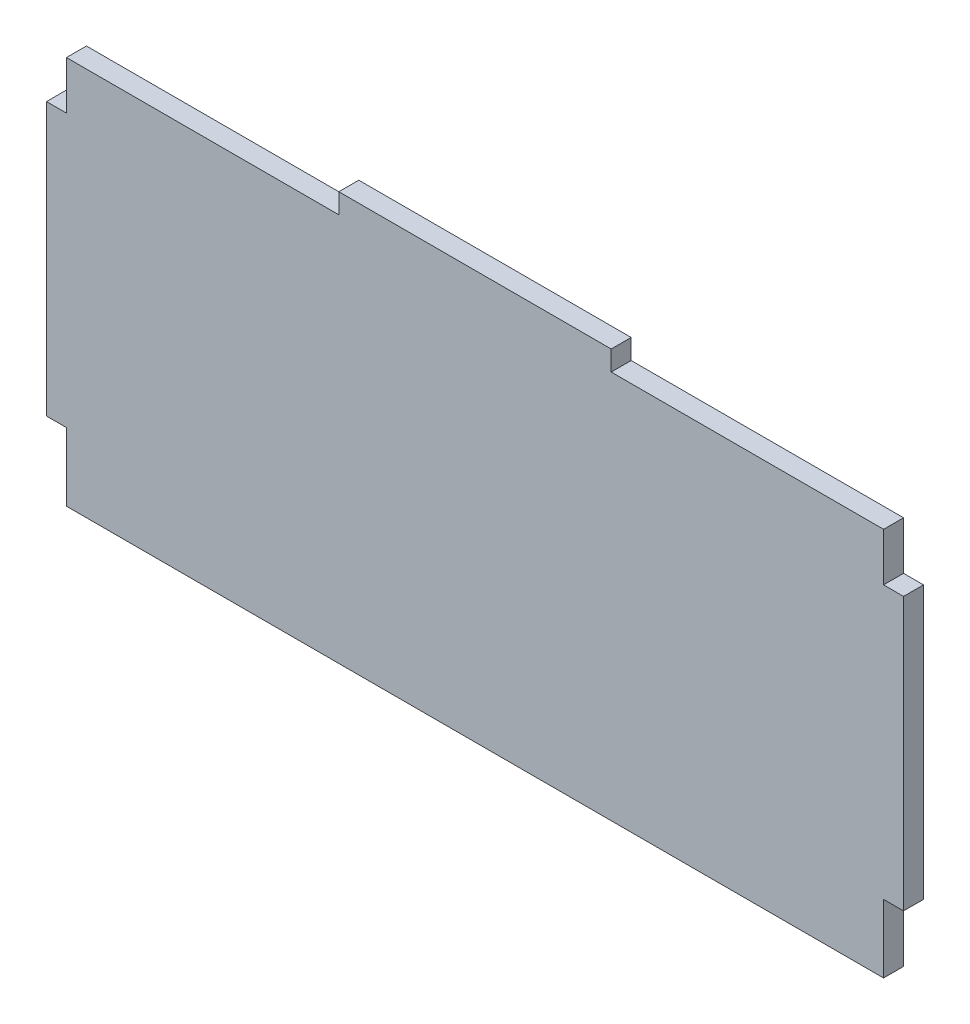
SolidWorks part; units mm, degrees
ref_plane "Front Plane" through (0, 0, 0) normal (0, 0, 1) x (1, 0, 0)
ref_plane "Top Plane" through (0, 0, 0) normal (0, 1, 0) x (1, 0, 0)
ref_plane "Right Plane" through (0, 0, 0) normal (1, 0, 0) x (0, 0, -1)
sketch "Sketch1" plane through (0, 0, 0) normal (0, 0, 1) x (1, 0, 0)
  line L0 (184.6217, 2.207) -> (184.6217, 42.536) construction
  line L1 (-49.5663, 19.0519) -> (179.0337, 19.0519)
  line L2 (-49.5663, 19.0519) -> (-49.5663, -89.6601)
  line L3 (-49.5663, -89.6601) -> (179.0337, -89.6601)
  line L4 (179.0337, 19.0519) -> (179.0337, -89.6601)
  line L5 (-55.1543, 5.5899) -> (-49.5663, 5.5899)
  line L6 (-55.1543, 5.5899) -> (-55.1543, -70.6101)
  line L7 (-55.1543, -70.6101) -> (-49.5663, -70.6101)
  line L8 (-49.5663, 5.5899) -> (-49.5663, -70.6101)
  line L9 (179.0337, 5.5899) -> (184.6217, 5.5899)
  line L10 (179.0337, 5.5899) -> (179.0337, -70.6101)
  line L11 (179.0337, -70.6101) -> (184.6217, -70.6101)
  line L12 (184.6217, 5.5899) -> (184.6217, -70.6101)
  line L13 (26.6337, 24.6399) -> (102.8337, 24.6399)
  line L14 (26.6337, 24.6399) -> (26.6337, 19.0519)
  line L15 (26.6337, 19.0519) -> (102.8337, 19.0519)
  line L16 (102.8337, 24.6399) -> (102.8337, 19.0519)
  dimension "D1" = 228.6
  dimension "D2" = 108.712
  dimension "D3" = 76.2
  dimension "D5" = 5.588
  dimension "D6" = 5.588
  dimension "D7" = 76.2
  dimension "D9" = 5.588
  dimension "D10" = 76.2
  dimension "D11" = 76.2
  dimension "D4" = 13.462
  dimension "D8" = 13.462
extrude "Boss-Extrude1" add sketch "Sketch1" along normal blind 5.588 contours L4 L1 L2 L3 | L16 L13 L14 L1 | L12 L9 L4 L11 | L6 L7 L2 L5 region at (64.7337, -35.3041, 0) region at (64.7337, 21.8459, 0) region at (-52.3603, -32.5101, 0) region at (181.8277, -32.5101, 0)
equation "\"width\"= 9in"
equation "\"Height\"= 18in"
equation "\"thick\"= 0.22"
equation "\"D1@Sketch1\"=\"width\""
equation "\"D2@Sketch1\"=(\"width\"/2)-\"thick\""
equation "\"D5@Sketch1\"=\"thick\""
equation "\"D6@Sketch1\"=\"thick\""
equation "\"D7@Sketch1\"=3"
equation "\"D9@Sketch1\"=\"thick\""
equation "\"D1@Boss-Extrude1\"=\"thick\""
equation "\"D4@Sketch1\"=0.75-\"thick\""
equation "\"D8@Sketch1\"=0.75-\"thick\""
